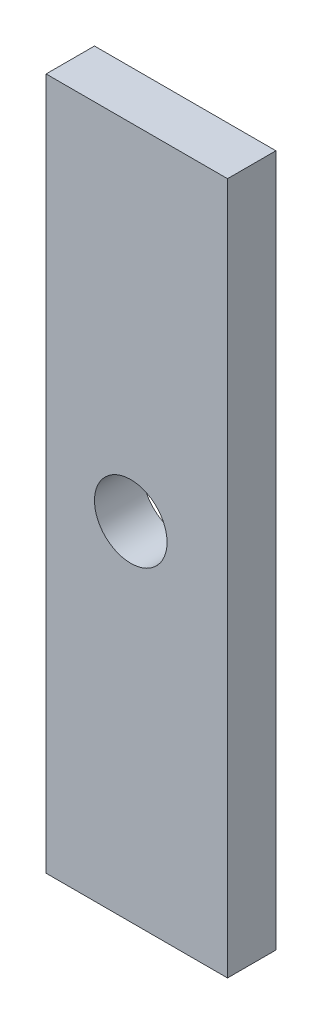
SolidWorks part; units mm, degrees
ref_plane "Front Plane" through (0, 0, 0) normal (0, 0, 1) x (1, 0, 0)
ref_plane "Top Plane" through (0, 0, 0) normal (0, 1, 0) x (1, 0, 0)
ref_plane "Right Plane" through (0, 0, 0) normal (1, 0, 0) x (0, 0, -1)
sketch "Sketch1" plane through (0, 0, 0) normal (0, 0, 1) x (1, 0, 0)
  line L0 (-3.5, 14.272) -> (4, 14.272)
  line L1 (-3.5, -14.3466) -> (4, -14.3466)
  line L2 (4, -14.3466) -> (4, 14.272)
  line L3 (-3.5, 14.272) -> (-3.5, -14.3466)
  circle A0 centre (0, 0) radius 1.5
  dimension "D1" = 7.5
  dimension "D4" = 3
  dimension "D2" = 28.6186
  dimension "D3" = 4
extrude "Boss-Extrude1" add sketch "Sketch1" along normal blind 2
